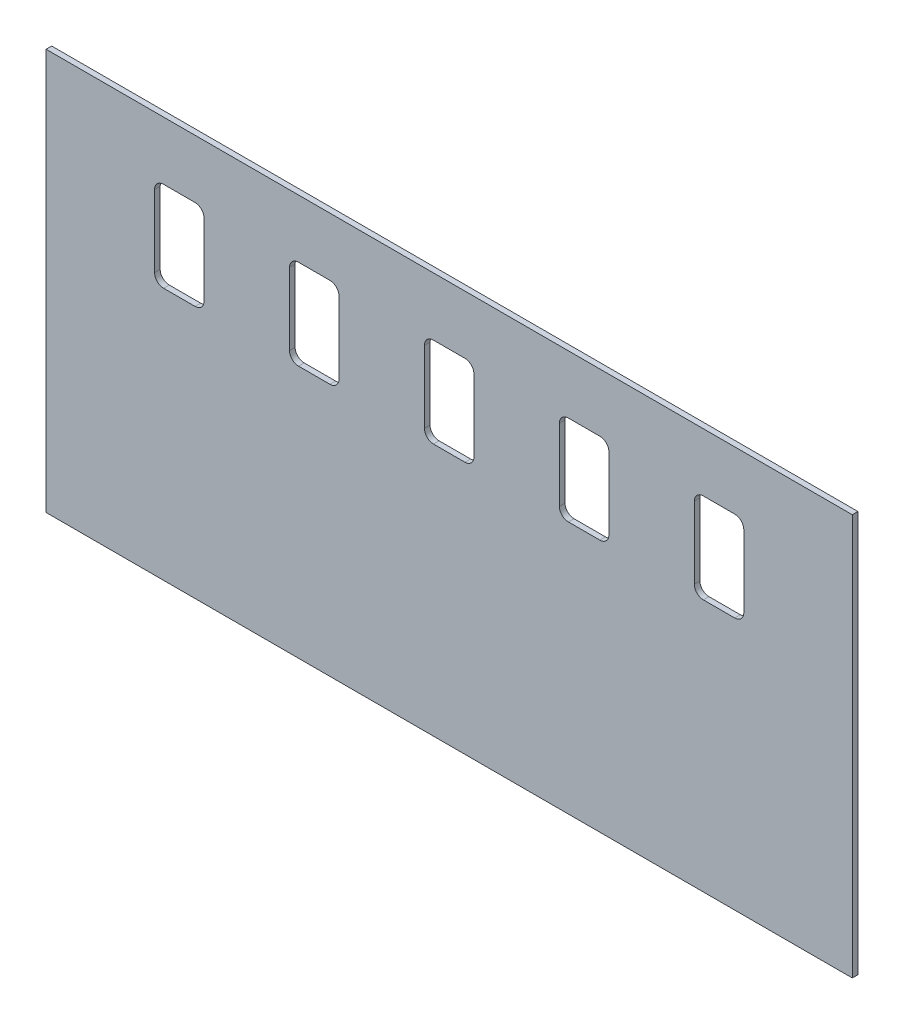
SolidWorks part; units mm, degrees
material "PBT General Purpose"
ref_plane "Front Plane" through (0, 0, 0) normal (0, 0, 1) x (1, 0, 0)
ref_plane "Top Plane" through (0, 0, 0) normal (0, 1, 0) x (1, 0, 0)
ref_plane "Right Plane" through (0, 0, 0) normal (1, 0, 0) x (0, 0, -1)
sketch "Sketch1" plane through (0, 0, 0) normal (0, 0, 1) x (1, 0, 0)
  line L1 (-227.6475, -113.284) -> (227.6475, -113.284)
  line L2 (-227.6475, -113.284) -> (-227.6475, 113.284)
  line L3 (-227.6475, 113.284) -> (227.6475, 113.284)
  line L4 (227.6475, -113.284) -> (227.6475, 113.284)
  line L5 (0, 113.284) -> (0, -113.284) construction
  line L6 (-227.6475, 0) -> (227.6475, 0) construction
  point P0 (0, 0)
  point P4 (-159.0675, 0)
  point P5 (159.0675, 0)
  point P6 (0, 79.2988)
  point P7 (0, -79.2988)
  dimension "Width" = 226.568
  dimension "Break" = 68.58
  dimension "D2" = 68.58
  dimension "D1" = 33.9852
  dimension "D3" = 33.9852
  dimension "D4" = 455.295
sketch "Sketch2" plane through (0, 0, 0) normal (1, 0, 0) x (0, 0, -1)
  line L0 (-1.5875, -113.284) -> (1.5875, -113.284)
  dimension "Thickness" = 3.175
sketch "Sketch3" plane through (0, 0, 0) normal (0, 0, 1) x (1, 0, 0)
  line L0 (-227.6475, -113.284) -> (-227.6475, 113.284) construction
  line L1 (-227.6475, -113.284) -> (227.6475, -113.284) construction
  line L2 (227.6475, -113.284) -> (227.6475, 113.284) construction
  line L3 (-227.6475, 113.284) -> (227.6475, 113.284) construction
  line L4 (-227.6475, -113.284) -> (-227.6475, 113.284)
  line L5 (-227.6475, -113.284) -> (227.6475, -113.284)
  line L6 (227.6475, -113.284) -> (227.6475, 113.284)
  line L7 (-227.6475, 113.284) -> (227.6475, 113.284)
extrude "Boss-Extrude1" add sketch "Sketch3" along normal mid plane 3.175
sketch "Sketch4" plane through (0, 0, 1.5875) normal (0, 0, 1) x (1, 0, 0)
  line L0 (-227.6475, 54.991) -> (-158.75, 54.991) construction
  line L1 (-82.55, 54.991) -> (-82.55, 80.391) construction
  line L2 (-82.55, 80.391) -> (-90.17, 80.391) construction
  line L3 (-158.75, 54.991) -> (-158.75, 80.391) construction
  line L8 (-158.75, 54.991) -> (-82.55, 54.991) construction
  line L9 (-82.55, 54.991) -> (-6.35, 54.991) construction
  line L10 (-6.35, 54.991) -> (69.85, 54.991) construction
  line L11 (69.85, 54.991) -> (146.05, 54.991) construction
  line L12 (-82.55, 54.991) -> (-82.55, 29.591) construction
  line L13 (-82.55, 29.591) -> (-62.23, 29.591) construction
  line L16 (-158.75, 80.391) -> (-166.37, 80.391) construction
  line L17 (-158.75, 54.991) -> (-158.75, 29.591) construction
  line L18 (-158.75, 29.591) -> (-138.43, 29.591) construction
  line L19 (-6.35, 54.991) -> (-6.35, 80.391) construction
  line L20 (-161.29, 80.391) -> (-143.51, 80.391)
  line L21 (-166.37, 75.311) -> (-166.37, 34.671)
  line L22 (-161.29, 29.591) -> (-143.51, 29.591)
  line L23 (-138.43, 75.311) -> (-138.43, 34.671)
  line L24 (-6.35, 80.391) -> (-13.97, 80.391) construction
  line L25 (-6.35, 54.991) -> (-6.35, 29.591) construction
  line L26 (-6.35, 29.591) -> (13.97, 29.591) construction
  line L27 (69.85, 54.991) -> (69.85, 80.391) construction
  line L28 (-8.89, 80.391) -> (8.89, 80.391)
  line L29 (-13.97, 75.311) -> (-13.97, 34.671)
  line L30 (-8.89, 29.591) -> (8.89, 29.591)
  line L31 (13.97, 75.311) -> (13.97, 34.671)
  line L32 (69.85, 80.391) -> (62.23, 80.391) construction
  line L33 (69.85, 54.991) -> (69.85, 29.591) construction
  line L34 (69.85, 29.591) -> (90.17, 29.591) construction
  line L35 (146.05, 54.991) -> (146.05, 80.391) construction
  line L36 (67.31, 80.391) -> (85.09, 80.391)
  line L37 (62.23, 75.311) -> (62.23, 34.671)
  line L38 (67.31, 29.591) -> (85.09, 29.591)
  line L39 (90.17, 75.311) -> (90.17, 34.671)
  line L40 (146.05, 80.391) -> (138.43, 80.391) construction
  line L41 (146.05, 54.991) -> (146.05, 29.591) construction
  line L42 (146.05, 29.591) -> (166.37, 29.591) construction
  line L44 (143.51, 80.391) -> (161.29, 80.391)
  line L45 (138.43, 75.311) -> (138.43, 34.671)
  line L46 (143.51, 29.591) -> (161.29, 29.591)
  line L47 (166.37, 75.311) -> (166.37, 34.671)
  line L48 (-85.09, 80.391) -> (-67.31, 80.391)
  line L49 (-90.17, 75.311) -> (-90.17, 34.671)
  line L50 (-85.09, 29.591) -> (-67.31, 29.591)
  line L51 (-62.23, 75.311) -> (-62.23, 34.671)
  arc A0 (138.43, 34.671) -> (143.51, 29.591) centre (143.51, 34.671) ccw
  arc A1 (166.37, 34.671) -> (161.29, 29.591) centre (161.29, 34.671) cw
  arc A2 (161.29, 80.391) -> (166.37, 75.311) centre (161.29, 75.311) cw
  arc A3 (138.43, 75.311) -> (143.51, 80.391) centre (143.51, 75.311) cw
  arc A4 (62.23, 34.671) -> (67.31, 29.591) centre (67.31, 34.671) ccw
  arc A5 (90.17, 34.671) -> (85.09, 29.591) centre (85.09, 34.671) cw
  arc A6 (85.09, 80.391) -> (90.17, 75.311) centre (85.09, 75.311) cw
  arc A7 (67.31, 80.391) -> (62.23, 75.311) centre (67.31, 75.311) ccw
  arc A8 (-13.97, 34.671) -> (-8.89, 29.591) centre (-8.89, 34.671) ccw
  arc A9 (13.97, 34.671) -> (8.89, 29.591) centre (8.89, 34.671) cw
  arc A10 (8.89, 80.391) -> (13.97, 75.311) centre (8.89, 75.311) cw
  arc A11 (-8.89, 80.391) -> (-13.97, 75.311) centre (-8.89, 75.311) ccw
  arc A15 (-138.43, 34.671) -> (-143.51, 29.591) centre (-143.51, 34.671) cw
  arc A16 (-143.51, 80.391) -> (-138.43, 75.311) centre (-143.51, 75.311) cw
  arc A17 (-166.37, 75.311) -> (-161.29, 80.391) centre (-161.29, 75.311) cw
  arc A18 (-166.37, 34.671) -> (-161.29, 29.591) centre (-161.29, 34.671) ccw
  arc A19 (-90.17, 34.671) -> (-85.09, 29.591) centre (-85.09, 34.671) ccw
  arc A20 (-62.23, 34.671) -> (-67.31, 29.591) centre (-67.31, 34.671) cw
  arc A21 (-67.31, 80.391) -> (-62.23, 75.311) centre (-67.31, 75.311) cw
  arc A22 (-85.09, 80.391) -> (-90.17, 75.311) centre (-85.09, 75.311) ccw
  point P14 (-152.4, 80.391)
  point P15 (-227.6475, 54.991)
  point P16 (-76.2, 80.391)
  point P17 (-90.17, 54.991)
  point P18 (-13.97, 54.991)
  point P95 (62.23, 54.991)
  point P96 (138.43, 54.991)
  point P97 (0, 80.391)
  point P98 (76.2, 80.391)
  point P99 (152.4, 80.391)
  dimension "D1" = 5.08
  dimension "D2" = 5.08
  dimension "D8" = 27.94
  dimension "D9" = 27.94
  dimension "D10" = 27.94
  dimension "D11" = 27.94
  dimension "D12" = 27.94
  dimension "D4" = 76.2
  dimension "D5" = 152.4
  dimension "D6" = 152.4
  dimension "D13" = 25.4
  dimension "D14" = 25.4
extrude "Cut-Extrude1" cut sketch "Sketch4" against normal blind 25.4 contours L21 A18 L22 A15 L23 A16 L20 A17 | A22 L48 A21 L51 A20 L50 A19 L49 | L29 A8 L30 A9 L31 A10 L28 A11 | L37 A4 L38 A5 L39 A6 L36 A7 | A3 L44 A2 L47 A1 L46 A0 L45
equation "\"D1@Boss-Extrude1\" = \"Thickness@Sketch2\""
equation "\"D2@Sketch1\" = \"Break@Sketch1\""
equation "\"D1@Sketch1\"=\"Width@Sketch1\"*0.15"
equation "\"D3@Sketch1\"=\"D1@Sketch1\""
equation "\"SlotWidth\"= 1.1in"
equation "\"D8@Sketch4\"=\"SlotWidth\""
equation "\"D9@Sketch4\"=\"SlotWidth\""
equation "\"D10@Sketch4\"=\"SlotWidth\""
equation "\"D11@Sketch4\"=\"SlotWidth\""
equation "\"D12@Sketch4\"=\"SlotWidth\""
